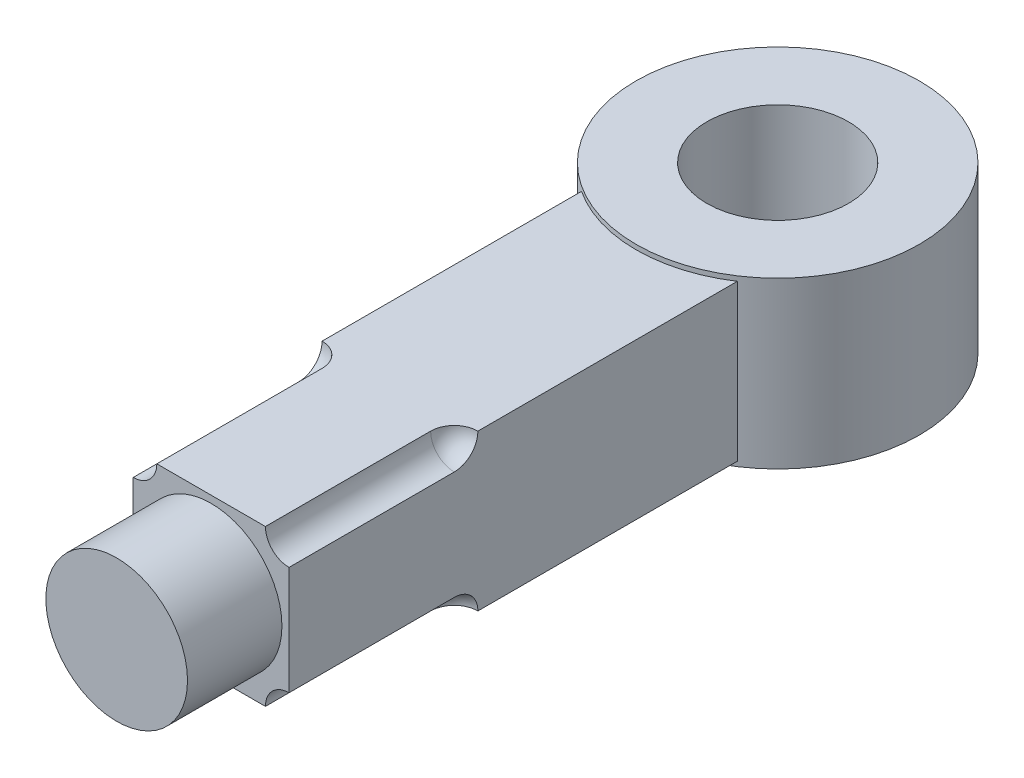
SolidWorks part; units mm, degrees
ref_plane "Front Plane" through (0, 0, 0) normal (0, 0, 1) x (1, 0, 0)
ref_plane "Top Plane" through (0, 0, 0) normal (0, 1, 0) x (1, 0, 0)
ref_plane "Right Plane" through (0, 0, 0) normal (1, 0, 0) x (0, 0, -1)
sketch "Sketch1" plane through (0, 0, 0) normal (0, 1, 0) x (1, 0, 0)
  circle A0 centre (0, 0) radius 30
  dimension "D1" = 60
extrude "Boss-Extrude1" add sketch "Sketch1" along normal mid plane 35
sketch "Sketch2" plane through (0, 0, 0) normal (0, 0, 1) x (1, 0, 0)
  line L1 (16.5, 16.5) -> (-16.5, 16.5)
  line L2 (16.5, 16.5) -> (16.5, -16.5)
  line L3 (16.5, -16.5) -> (-16.5, -16.5)
  line L4 (-16.5, 16.5) -> (-16.5, -16.5)
  line L5 (16.5, 16.5) -> (-16.5, -16.5) construction
  line L6 (16.5, -16.5) -> (-16.5, 16.5) construction
  point P0 (0, 0)
  dimension "D1" = 33
  dimension "D2" = 33
extrude "Boss-Extrude2" add sketch "Sketch2" along normal blind 120
sketch "Sketch3" plane through (0, 0, 120) normal (0, 0, 1) x (1, 0, 0)
  circle A0 centre (0, 0) radius 15
  dimension "D1" = 30
extrude "Boss-Extrude3" add sketch "Sketch3" along normal blind 20
hole_wizard "Hole1" positions "Sketch4" profile "Sketch5" legacy end condition through all
sketch "Sketch4" plane through (0, 17.5, 0) normal (0, 1, 0) x (1, 0, 0)
  point P0 (0, 0)
sketch "Sketch5" plane through (0, 17.5, 0) normal (1, 0, 0) x (0, 0, 1)
  line L0 (0, 0) -> (0, 35)
  line L1 (0, 35) -> (15, 35)
  line L2 (15, 35) -> (15, 0)
  line L3 (15, 0) -> (0, 0)
  line L4 (0, 110) -> (0, -10) construction
  dimension "Diameter" = 30
  dimension "Depth" = 35
sketch "Sketch6" plane through (0, 0, 120) normal (0, 0, 1) x (1, 0, 0)
  line L0 (16.5, 16.5) -> (-16.5, 16.5) construction
  line L1 (16.5, -16.5) -> (16.5, 16.5) construction
  line L2 (11.5, 16.5) -> (16.5, 16.5)
  line L3 (16.5, 16.5) -> (16.5, 11.5)
  arc A0 (11.5, 16.5) -> (16.5, 11.5) centre (16.5, 16.5) ccw
  dimension "D1" = 5
extrude "Cut-Extrude1" cut sketch "Sketch6" against normal blind 40
fillet "Fillet1" radius 5 1 edges at (12.9645, 12.9645, 80)
pattern_circular "CirPattern1" count 4 over 360 about axis through (0, 0, 140) along (0, 0, 1) of "Cut-Extrude1", "Fillet1"
